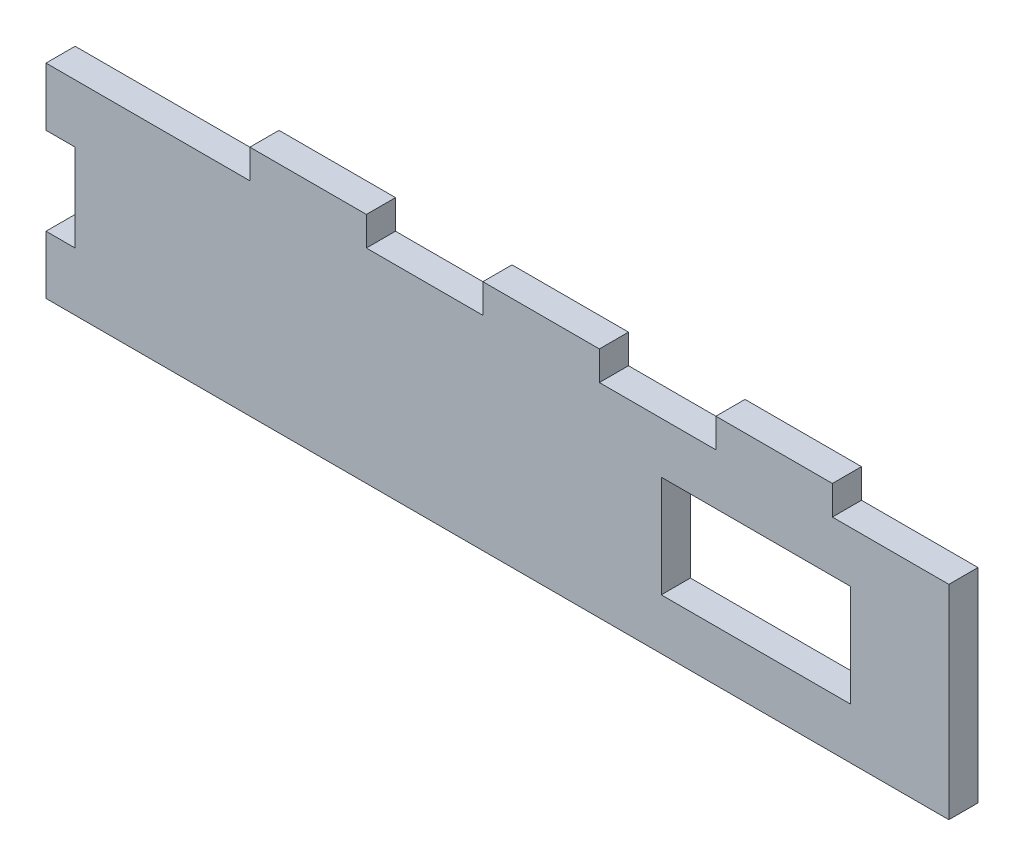
SolidWorks part; units mm, degrees
ref_plane "Front Plane" through (0, 0, 0) normal (0, 0, 1) x (1, 0, 0)
ref_plane "Top Plane" through (0, 0, 0) normal (0, 1, 0) x (1, 0, 0)
ref_plane "Right Plane" through (0, 0, 0) normal (1, 0, 0) x (0, 0, -1)
sketch "Sketch1" plane through (0, 0, 0) normal (0, 0, 1) x (1, 0, 0)
  line L0 (69.2576, 0) -> (-63.1151, 0) construction
  line L1 (42.067, 22.225) -> (-148.433, 22.225)
  line L2 (42.067, 22.225) -> (42.067, -22.225)
  line L3 (42.067, -22.225) -> (-148.433, -22.225)
  line L4 (-148.433, 22.225) -> (-148.433, -22.225)
  line L7 (25.98, 9.3599) -> (20.1295, 9.3599) construction
  line L8 (20.1295, -9.3599) -> (25.98, -9.3599) construction
  line L9 (-148.433, -69.85) -> (-148.433, 54.9538) construction
  line L10 (27.25, 6.27) -> (27.25, 8.0899) construction
  dimension "D1" = 44.45
  dimension "D2" = 14.817
extrude "Boss-Extrude1" add sketch "Sketch1" along normal blind 6.35
sketch "Sketch2" plane through (0, 0, 6.35) normal (0, 0, 1) x (1, 0, 0)
  line L0 (-43.1818, 0) -> (35.1848, 0) construction
  line L1 (-20.6375, 11.1125) -> (20.6375, 11.1125)
  line L2 (-20.6375, 11.1125) -> (-20.6375, -11.1125)
  line L3 (-20.6375, -11.1125) -> (20.6375, -11.1125)
  line L4 (20.6375, 11.1125) -> (20.6375, -11.1125)
  line L5 (-19.6295, 10.033) -> (19.6295, 10.033) construction
  line L6 (19.6295, -10.033) -> (-19.6295, -10.033) construction
  line L7 (0, 18.8234) -> (0, -13.1279) construction
  line L8 (-20.1295, -9.533) -> (-20.1295, 9.533) construction
  line L9 (20.1295, 9.533) -> (20.1295, -9.533) construction
  dimension "D1" = 22.225
  dimension "D2" = 41.275
extrude "Cut-Extrude1" cut sketch "Sketch2" against normal through all
sketch "Sketch3" plane through (0, 22.225, 0) normal (0, 1, 0) x (1, 0, 0)
  line L0 (16.667, 0) -> (16.667, -6.35)
  line L1 (42.067, 0) -> (-148.433, 0) construction
  line L2 (42.067, -6.35) -> (-148.433, -6.35) construction
  line L3 (16.667, -6.35) -> (-8.733, -6.35)
  line L4 (-8.733, -6.35) -> (-8.733, 0)
  line L5 (-8.733, 0) -> (16.667, 0)
  dimension "D1" = 25.4
  dimension "D2" = 25.4
extrude "Boss-Extrude2" add sketch "Sketch3" along normal blind 6.35
pattern_linear "LPattern1" count 3 spacing 50.8 along (-1, 0, 0) of "Boss-Extrude2"
sketch "Sketch4" plane through (-148.433, 0, 0) normal (-1, 0, 0) x (0, 0, 1)
  line L0 (6.35, 22.225) -> (6.35, 9.525)
  line L1 (6.35, 22.225) -> (6.35, -22.225) construction
  line L2 (6.35, 9.525) -> (0, 9.525)
  line L3 (0, 22.225) -> (0, -22.225) construction
  line L4 (0, 9.525) -> (0, 22.225)
  line L5 (0, 22.225) -> (6.35, 22.225)
  dimension "D1" = 12.7
extrude "Boss-Extrude3" add sketch "Sketch4" along normal blind 6.35
pattern_linear "LPattern2" count 2 spacing 31.75 along (0, -1, 0) of "Boss-Extrude3"
